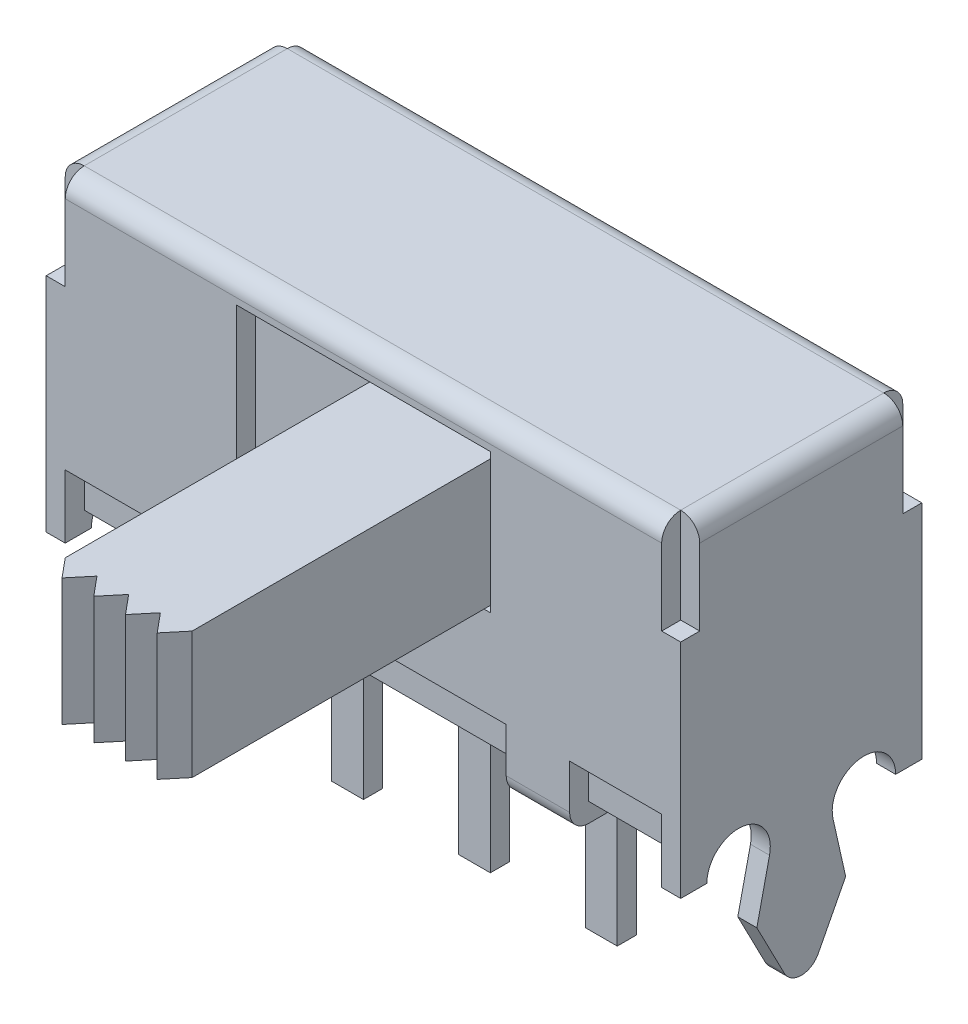
SolidWorks part; units mm, degrees
ref_plane "Front Plane" through (0, 0, 0) normal (0, 0, 1) x (1, 0, 0)
ref_plane "Top Plane" through (0, 0, 0) normal (0, 1, 0) x (1, 0, 0)
ref_plane "Right Plane" through (0, 0, 0) normal (1, 0, 0) x (0, 0, -1)
sketch "Sketch2" plane through (0, 0, 0) normal (1, 0, 0) x (0, 0, -1)
  line L0 (0, 5) -> (0, 0.9413) construction
  line L1 (-1.6, 5) -> (1.6, 5)
  line L2 (-1.9, 4.7) -> (-1.9, 0)
  line L3 (-1.9, 0) -> (-1.4878, 0)
  line L4 (1.9, 4.7) -> (1.9, 0)
  line L5 (-0.5, -0.1096) -> (-0.7, -1)
  line L6 (-0.7, -1) -> (-0.2664, -1.8379)
  line L7 (1.4878, 0) -> (1.9, 0)
  line L8 (0.7, -1) -> (0.2664, -1.8379)
  line L9 (0.5, -0.1096) -> (0.7, -1)
  arc A0 (-0.5, -0.1096) -> (-1.4878, 0) centre (-0.9878, 0) ccw
  arc A1 (-0.2664, -1.8379) -> (0.2664, -1.8379) centre (0, -1.7) ccw
  arc A2 (0.5, -0.1096) -> (1.4878, 0) centre (0.9878, 0) cw
  arc A3 (1.6, 5) -> (1.9, 4.7) centre (1.6, 4.7) cw
  arc A4 (-1.6, 5) -> (-1.9, 4.7) centre (-1.6, 4.7) ccw
  dimension "D4" = 1
  dimension "D3" = 1
  dimension "D6" = 0.3
  dimension "D7" = 0.5
  dimension "D9" = 0.3
  dimension "D1" = 5
  dimension "D2" = 3.8
  dimension "D5" = 1.4
  dimension "D8" = 1
extrude "Boss-Extrude1" add sketch "Sketch2" along normal mid plane 10
sketch "Sketch3" plane through (0, 0, 0) normal (0, -1, 0) x (1, 0, 0)
  line L0 (0, 0) -> (0, 0.15) construction
  line L1 (-2.25, 0.15) -> (-1.75, 0.15)
  line L2 (-2.25, 0.15) -> (-2.25, -0.15)
  line L3 (-2.25, -0.15) -> (-1.75, -0.15)
  line L4 (-1.75, 0.15) -> (-1.75, -0.15)
  line L5 (-0.25, 0.15) -> (0.25, 0.15)
  line L6 (-0.25, 0.15) -> (-0.25, -0.15)
  line L7 (-0.25, -0.15) -> (0.25, -0.15)
  line L8 (0.25, 0.15) -> (0.25, -0.15)
  line L9 (1.75, 0.15) -> (2.25, 0.15)
  line L10 (1.75, 0.15) -> (1.75, -0.15)
  line L11 (1.75, -0.15) -> (2.25, -0.15)
  line L12 (2.25, 0.15) -> (2.25, -0.15)
  line L13 (2, 0.15) -> (2, 0.3949) construction
  line L14 (-2, 0.15) -> (-2, 0.3949) construction
  line L15 (5, 1.9) -> (-5, 1.9) construction
  line L16 (-4.7, 1.9) -> (-5, 1.9)
  line L17 (-4.7, 1.9) -> (-4.7, -1.9)
  line L18 (-4.7, -1.9) -> (-5, -1.9)
  line L19 (-5, 1.9) -> (-5, -1.9)
  line L20 (5, 1.9) -> (5, 1.4878) construction
  line L21 (4.7, 1.9) -> (5, 1.9)
  line L22 (4.7, 1.9) -> (4.7, -1.9)
  line L23 (4.7, -1.9) -> (5, -1.9)
  line L24 (5, 1.9) -> (5, -1.9)
  line L25 (-5, 1.9) -> (-5, 1.4878) construction
  line L26 (5, -1.9) -> (-5, -1.9) construction
  dimension "D1" = 0.3
  dimension "D2" = 0.15
  dimension "D3" = 0.5
  dimension "D4" = 2
  dimension "D5" = 2
  dimension "D6" = 0.3
  dimension "D7" = 0.3
extrude "Cut-Extrude1" cut sketch "Sketch3" along normal through all flip side to cut
sketch "Sketch4" plane through (0, 0, 0) normal (0, -1, 0) x (1, 0, 0)
  line L0 (-2.25, -0.15) -> (-1.75, -0.15) construction
  line L1 (-2.25, 0.15) -> (-2.25, -0.15) construction
  line L2 (-2.25, 0.15) -> (-1.75, 0.15) construction
  line L3 (-1.75, 0.15) -> (-1.75, -0.15) construction
  line L4 (-0.25, 0.15) -> (-0.25, -0.15) construction
  line L5 (-0.25, -0.15) -> (0.25, -0.15) construction
  line L6 (0.25, 0.15) -> (0.25, -0.15) construction
  line L7 (-0.25, 0.15) -> (0.25, 0.15) construction
  line L8 (1.75, 0.15) -> (1.75, -0.15) construction
  line L9 (1.75, 0.15) -> (2.25, 0.15) construction
  line L10 (2.25, 0.15) -> (2.25, -0.15) construction
  line L11 (1.75, -0.15) -> (2.25, -0.15) construction
  line L12 (-2.25, -0.15) -> (-1.75, -0.15)
  line L13 (-2.25, 0.15) -> (-2.25, -0.15)
  line L14 (-2.25, 0.15) -> (-1.75, 0.15)
  line L15 (-1.75, 0.15) -> (-1.75, -0.15)
  line L16 (-0.25, 0.15) -> (-0.25, -0.15)
  line L17 (-0.25, -0.15) -> (0.25, -0.15)
  line L18 (0.25, 0.15) -> (0.25, -0.15)
  line L19 (-0.25, 0.15) -> (0.25, 0.15)
  line L20 (1.75, 0.15) -> (1.75, -0.15)
  line L21 (1.75, 0.15) -> (2.25, 0.15)
  line L22 (2.25, 0.15) -> (2.25, -0.15)
  line L23 (1.75, -0.15) -> (2.25, -0.15)
extrude "Boss-Extrude2" add sketch "Sketch4" along normal blind 2.9
sketch "Sketch5" plane through (0, 0, 0) normal (0, -1, 0) x (1, 0, 0)
  line L0 (-4.7, -0.2664) -> (-4.7, 0.2664) construction
  line L1 (5, 1.9) -> (-5, 1.9) construction
  line L2 (-4.7, 1.9) -> (-3.25, 1.9)
  line L3 (-4.7, 1.9) -> (-4.7, 1.6)
  line L4 (-4.7, 1.6) -> (-3.25, 1.6)
  line L5 (4.7, 0.4878) -> (4.7, -0.4878) construction
  line L6 (-3.25, 1.9) -> (-3.25, 1.6)
  line L8 (-2.25, 1.9) -> (2.25, 1.9)
  line L9 (-2.25, 1.9) -> (-2.25, 1.6)
  line L10 (-2.25, 1.6) -> (2.25, 1.6)
  line L11 (2.25, 1.9) -> (2.25, 1.6)
  line L12 (3.25, 1.9) -> (4.7, 1.9)
  line L13 (3.25, 1.9) -> (3.25, 1.6)
  line L14 (3.25, 1.6) -> (4.7, 1.6)
  line L15 (4.7, 1.9) -> (4.7, 1.6)
  line L17 (-2.25, 0.15) -> (-2.25, -0.15) construction
  line L18 (2.25, -0.15) -> (2.25, 0.15) construction
  line L19 (0, 0) -> (-1.2064, 0) construction
  line L20 (4.7, -1.9) -> (4.7, -1.6)
  line L21 (3.25, -1.6) -> (4.7, -1.6)
  line L22 (3.25, -1.9) -> (3.25, -1.6)
  line L23 (3.25, -1.9) -> (4.7, -1.9)
  line L24 (2.25, -1.9) -> (2.25, -1.6)
  line L25 (-2.25, -1.6) -> (2.25, -1.6)
  line L26 (-2.25, -1.9) -> (-2.25, -1.6)
  line L27 (-2.25, -1.9) -> (2.25, -1.9)
  line L28 (-3.25, -1.9) -> (-3.25, -1.6)
  line L29 (-4.7, -1.6) -> (-3.25, -1.6)
  line L30 (-4.7, -1.9) -> (-4.7, -1.6)
  line L31 (-4.7, -1.9) -> (-3.25, -1.9)
  dimension "D1" = 0.3
  dimension "D2" = 1
  dimension "D3" = 1
extrude "Cut-Extrude2" cut sketch "Sketch5" against normal blind 1
sketch "Sketch6" plane through (0, 0, 0) normal (0, -1, 0) x (1, 0, 0)
  line L0 (-2.25, 0.15) -> (-2.25, -0.15) construction
  line L1 (-4.7, 1.6) -> (4.7, 1.6)
  line L2 (-4.7, 1.6) -> (-4.7, -1.6)
  line L3 (-4.7, -1.6) -> (4.7, -1.6)
  line L4 (4.7, 1.6) -> (4.7, -1.6)
  line L5 (-2.25, -0.15) -> (-1.75, -0.15) construction
  line L6 (-1.75, -0.15) -> (-1.75, 0.15) construction
  line L7 (-1.75, 0.15) -> (-2.25, 0.15) construction
  line L8 (0.25, 0.15) -> (-0.25, 0.15) construction
  line L9 (-0.25, 0.15) -> (-0.25, -0.15) construction
  line L10 (-0.25, -0.15) -> (0.25, -0.15) construction
  line L11 (0.25, -0.15) -> (0.25, 0.15) construction
  line L12 (2.25, 0.15) -> (1.75, 0.15) construction
  line L13 (1.75, 0.15) -> (1.75, -0.15) construction
  line L14 (1.75, -0.15) -> (2.25, -0.15) construction
  line L15 (2.25, -0.15) -> (2.25, 0.15) construction
  line L16 (-2.25, 0.15) -> (-2.25, -0.15)
  line L17 (-2.25, -0.15) -> (-1.75, -0.15)
  line L18 (-1.75, -0.15) -> (-1.75, 0.15)
  line L19 (-1.75, 0.15) -> (-2.25, 0.15)
  line L20 (0.25, 0.15) -> (-0.25, 0.15)
  line L21 (-0.25, 0.15) -> (-0.25, -0.15)
  line L22 (-0.25, -0.15) -> (0.25, -0.15)
  line L23 (0.25, -0.15) -> (0.25, 0.15)
  line L24 (2.25, 0.15) -> (1.75, 0.15)
  line L25 (1.75, 0.15) -> (1.75, -0.15)
  line L26 (1.75, -0.15) -> (2.25, -0.15)
  line L27 (2.25, -0.15) -> (2.25, 0.15)
extrude "Cut-Extrude3" cut sketch "Sketch6" against normal blind 0.3
sketch "Sketch7" plane through (0, 0.3, 0) normal (0, -1, 0) x (1, 0, 0)
  line L1 (-4.7, 1.6) -> (4.7, 1.6)
  line L2 (-4.7, 1.6) -> (-4.7, -1.6)
  line L3 (-4.7, -1.6) -> (4.7, -1.6)
  line L4 (4.7, 1.6) -> (4.7, -1.6)
extrude "Boss-Extrude3" add sketch "Sketch7" against normal up to surface (0.7 mm away) up to face at (-3.975, 1, 1.75)
sketch "Sketch8" plane through (0, 0, 0) normal (0, -1, 0) x (1, 0, 0)
  line L0 (-2.25, 1.9) -> (-2.25, 1.6) construction
  line L1 (-3.25, 1.9) -> (-2.25, 1.9)
  line L2 (-3.25, 1.9) -> (-3.25, 0.9)
  line L3 (-3.25, 0.9) -> (-2.25, 0.9)
  line L4 (-2.25, 1.9) -> (-2.25, 0.9)
  line L5 (2.25, 1.9) -> (3.25, 1.9)
  line L6 (2.25, 1.9) -> (2.25, 0.9)
  line L7 (2.25, 0.9) -> (3.25, 0.9)
  line L8 (3.25, 1.9) -> (3.25, 0.9)
  line L9 (2.25, -1.9) -> (3.25, -1.9)
  line L10 (2.25, -1.9) -> (2.25, -0.9)
  line L11 (2.25, -0.9) -> (3.25, -0.9)
  line L12 (3.25, -1.9) -> (3.25, -0.9)
  line L13 (-3.25, -1.9) -> (-2.25, -1.9)
  line L14 (-3.25, -1.9) -> (-3.25, -0.9)
  line L15 (-3.25, -0.9) -> (-2.25, -0.9)
  line L16 (-2.25, -1.9) -> (-2.25, -0.9)
  line L17 (-2.25, 1.9) -> (-2.25, 1.6) construction
  line L18 (3.25, 1.9) -> (3.25, 1.6) construction
  line L19 (3.25, 1.9) -> (3.25, 1.6) construction
  line L20 (-2.25, -1.6) -> (-2.25, -1.9) construction
  line L21 (-2.25, -1.6) -> (-2.25, -1.9) construction
  dimension "D1" = 1
  dimension "D2" = 1
extrude "Boss-Extrude4" add sketch "Sketch8" against normal up to surface (0.3 mm away) up to face at (0, 0.3, 0)
fillet "Fillet2" radius 0.3 6 edges at (-5, 5, 0) (5, 5, 0) (2.75, 0, 1.9) (2.75, 0, -1.9) (-2.75, 0, -1.9) (-2.75, 0, 1.9) tangent propagation no
sketch "Sketch9" plane through (0, 0, 1.9) normal (0, 0, 1) x (1, 0, 0)
  line L0 (0, 0.0415) -> (0, 5.2178) construction
  line L1 (-2, 4.6) -> (2, 4.6)
  line L2 (-2, 4.6) -> (-2, 2.4)
  line L3 (-2, 2.4) -> (2, 2.4)
  line L4 (2, 4.6) -> (2, 2.4)
  line L5 (-2, 3.5) -> (-2.655, 3.5) construction
  line L6 (-4.7, 0) -> (-5, 0) construction
  dimension "D1" = 2
  dimension "D2" = 4
  dimension "D3" = 3.5
  dimension "D4" = 2.2
extrude "Cut-Extrude4" cut sketch "Sketch9" against normal blind 0.3
sketch "Sketch10" plane through (0, 0, 1.6) normal (0, 0, 1) x (1, 0, 0)
  line L0 (0, 3.5) -> (-2, 3.5) construction
  line L1 (0, 4.5) -> (2, 4.5)
  line L2 (0, 4.5) -> (0, 2.5)
  line L3 (0, 2.5) -> (2, 2.5)
  line L4 (2, 4.5) -> (2, 2.5)
  line L5 (-2, 4.6) -> (-2, 2.4) construction
  line L7 (2, 2.4) -> (2, 4.6) construction
  dimension "D1" = 2
  dimension "D2" = 2
extrude "Boss-Extrude5" add sketch "Sketch10" along normal offset from surface (5.3 mm away) 5 up to face at (0, 3.5, 1.9) offset beyond the face yes
sketch "Sketch11" plane through (0, 4.5, 0) normal (0, 1, 0) x (1, 0, 0)
  line L0 (0, -6.6) -> (0.25, -6.9)
  line L1 (0, -6.9) -> (0, -1.6) construction
  line L2 (0, -6.9) -> (2, -6.9) construction
  line L3 (0.25, -6.9) -> (0.5, -6.6)
  line L4 (0.5, -6.6) -> (0.75, -6.9)
  line L5 (0.75, -6.9) -> (1, -6.6)
  line L6 (1, -6.6) -> (1.25, -6.9)
  line L7 (1.25, -6.9) -> (1.5, -6.6)
  line L8 (1.5, -6.6) -> (1.75, -6.9)
  line L9 (1.75, -6.9) -> (2, -6.6)
  line L10 (2, -6.9) -> (2, -1.9) construction
  line L11 (1, -6.9) -> (1, -6.0279) construction
  line L12 (0.25, -6.9) -> (0.75, -6.9) construction
  line L13 (0.75, -6.9) -> (1.25, -6.9) construction
  line L14 (1.25, -6.9) -> (1.75, -6.9) construction
  line L15 (0, -6.6) -> (0.5, -6.6) construction
  line L16 (0.5, -6.6) -> (1, -6.6) construction
  line L17 (1, -6.6) -> (1.5, -6.6) construction
  line L18 (1.5, -6.6) -> (2, -6.6) construction
  line L19 (0, -6.6) -> (-0.5, -6.6)
  line L20 (-0.5, -6.6) -> (-0.5, -7.4)
  line L21 (-0.5, -7.4) -> (2.5, -7.4)
  line L22 (2.5, -7.4) -> (2.5, -6.6)
  line L23 (2.5, -6.6) -> (2, -6.6)
  dimension "D1" = 0.3
  dimension "D2" = 0.5
  dimension "D3" = 0.5
  dimension "D4" = 0.5
extrude "Cut-Extrude5" cut sketch "Sketch11" against normal through all
sketch "Sketch12" plane through (0, -2.9, 0) normal (0, -1, 0) x (1, 0, 0)
  line L0 (-2.25, 0.15) -> (-1.75, -0.15) construction
  line L1 (1.75, 0.15) -> (2.25, -0.15) construction
  circle A0 centre (-2, 0) radius 0.125
  circle A1 centre (2, 0) radius 0.125
  dimension "D1" = 0.25
extrude "Cut-Extrude6" cut sketch "Sketch12" against normal blind 0.1
sketch "Sketch13" plane through (0, 5, 0) normal (0, 1, 0) x (1, 0, 0)
  line L1 (-5, -1.9) -> (-4.7, -1.9)
  line L2 (-5, -1.9) -> (-5, -1.6)
  line L3 (-5, -1.6) -> (-4.7, -1.6)
  line L4 (-4.7, -1.9) -> (-4.7, -1.6)
  line L5 (-4.7, 1.6) -> (-5, 1.6)
  line L6 (-4.7, 1.6) -> (-4.7, 1.9)
  line L7 (-4.7, 1.9) -> (-5, 1.9)
  line L8 (-5, 1.6) -> (-5, 1.9)
  line L9 (4.7, 1.6) -> (5, 1.6)
  line L10 (4.7, 1.6) -> (4.7, 1.9)
  line L11 (4.7, 1.9) -> (5, 1.9)
  line L12 (5, 1.6) -> (5, 1.9)
  line L13 (4.7, -1.6) -> (5, -1.6)
  line L14 (4.7, -1.6) -> (4.7, -1.9)
  line L15 (4.7, -1.9) -> (5, -1.9)
  line L16 (5, -1.6) -> (5, -1.9)
extrude "Cut-Extrude7" cut sketch "Sketch13" against normal blind 1.5
